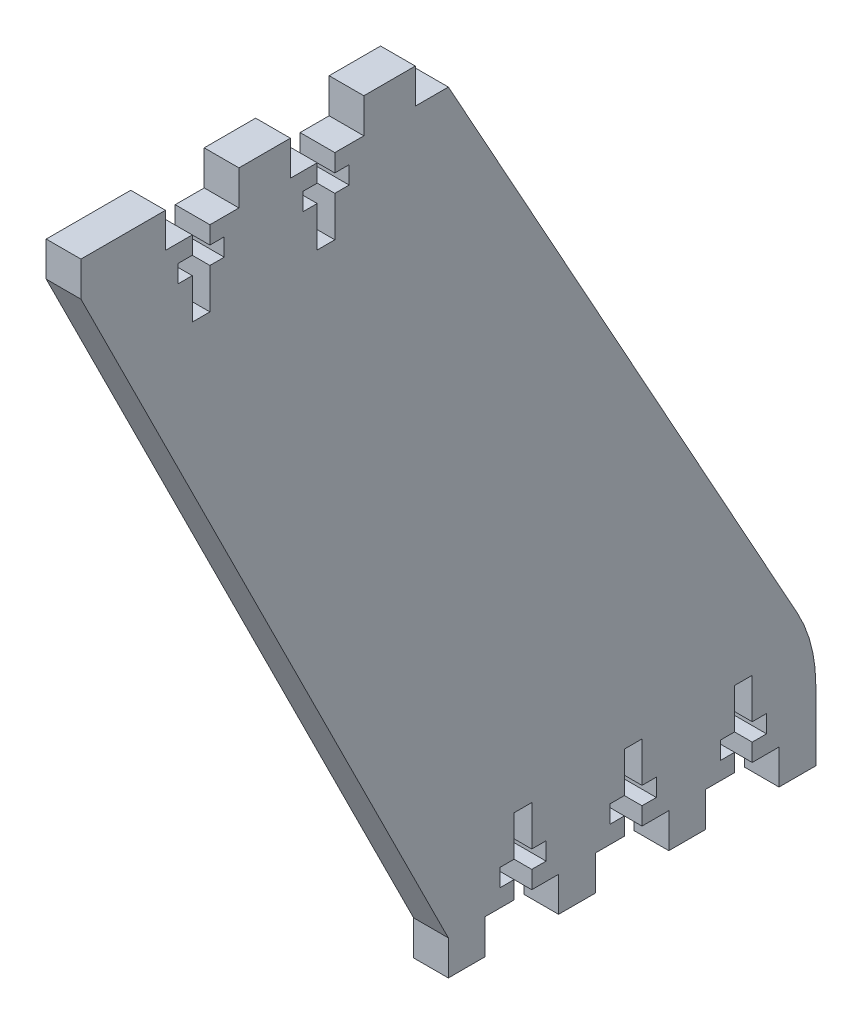
SolidWorks part; units mm, degrees
ref_plane "Front Plane" through (0, 0, 0) normal (0, 0, 1) x (1, 0, 0)
ref_plane "Top Plane" through (0, 0, 0) normal (0, 1, 0) x (1, 0, 0)
ref_plane "Right Plane" through (0, 0, 0) normal (1, 0, 0) x (0, 0, -1)
sketch "Sketch1" plane through (0, 0, 0) normal (1, 0, 0) x (0, 0, -1)
  line L0 (-74.3254, 0) -> (74.3254, 0) construction
  line L1 (-31.75, 0) -> (-95.25, 127.35)
  line L4 (-31.75, 0) -> (0, 17.1799) construction
  line L5 (-95.25, 127.35) -> (-95.25, 133.35)
  line L6 (-95.25, 133.35) -> (-80.645, 133.35)
  line L7 (-80.645, 133.35) -> (-80.645, 127.35)
  line L8 (-80.645, 127.35) -> (-67.945, 127.35)
  line L9 (-67.945, 127.35) -> (-67.945, 133.35)
  line L10 (-67.945, 133.35) -> (-59.055, 133.35)
  line L11 (-59.055, 133.35) -> (-59.055, 127.35)
  line L12 (-59.055, 127.35) -> (-46.355, 127.35)
  line L13 (-46.355, 127.35) -> (-46.355, 133.35)
  line L14 (-46.355, 133.35) -> (-37.465, 133.35)
  line L15 (-37.465, 133.35) -> (-37.465, 127.35)
  line L16 (-37.465, 127.35) -> (-31.75, 127.35)
  line L17 (-31.75, 0) -> (-31.75, -6)
  line L18 (-31.75, -6) -> (-25.4, -6)
  line L19 (-25.4, -6) -> (-25.4, 0)
  line L20 (-25.4, 0) -> (-12.7, 0)
  line L21 (-12.7, 0) -> (-12.7, -6)
  line L22 (-12.7, -6) -> (-6.35, -6)
  line L23 (-6.35, -6) -> (-6.35, 0)
  line L24 (-6.35, 0) -> (6.35, 0)
  line L25 (6.35, 0) -> (6.35, -6)
  line L26 (6.35, -6) -> (12.7, -6)
  line L27 (12.7, -6) -> (12.7, 0)
  line L28 (12.7, 0) -> (25.4, 0)
  line L29 (25.4, 0) -> (25.4, -6)
  line L30 (25.4, -6) -> (31.75, -6)
  line L31 (31.75, -6) -> (31.75, 0)
  line L32 (0, 17.1799) -> (31.75, 0) construction
  line L33 (0, 0) -> (0, 17.1799) construction
  line L34 (-63.5, 133.35) -> (-63.5, 108.2099) construction
  line L35 (31.75, 0) -> (31.75, 6.1358)
  line L36 (28.5696, 18.4423) -> (-31.75, 127.35)
  arc A0 (31.75, 6.1358) -> (28.5696, 18.4423) centre (6.35, 6.1358) ccw
  point P37 (-74.295, 127.35)
  point P38 (-52.705, 127.35)
  point P39 (-19.05, 0)
  point P40 (19.05, 0)
  point P44 (31.75, 12.7)
  line B0 (-18.8595, 13.05) -> (-18.8595, -5.9362) construction
  line B1 (-20.3835, 0) -> (-20.3835, 3.048)
  line B2 (-20.3835, 3.048) -> (-22.86, 3.048)
  line B3 (-22.86, 3.048) -> (-22.86, 6.096)
  line B4 (-22.86, 6.096) -> (-20.3835, 6.096)
  line B5 (-20.3835, 6.096) -> (-20.3835, 13.05)
  line B6 (-20.3835, 13.05) -> (-17.3355, 13.05)
  line B7 (-17.3355, 6.096) -> (-17.3355, 13.05)
  line B8 (-14.859, 6.096) -> (-17.3355, 6.096)
  line B9 (-14.859, 3.048) -> (-14.859, 6.096)
  line B10 (-17.3355, 3.048) -> (-14.859, 3.048)
  line B11 (-17.3355, 0) -> (-17.3355, 3.048)
  line B12 (0.1905, 13.05) -> (0.1905, -5.9362) construction
  line B13 (-1.3335, 0) -> (-1.3335, 3.048)
  line B14 (-1.3335, 3.048) -> (-3.81, 3.048)
  line B15 (-3.81, 3.048) -> (-3.81, 6.096)
  line B16 (-3.81, 6.096) -> (-1.3335, 6.096)
  line B17 (-1.3335, 6.096) -> (-1.3335, 13.05)
  line B18 (-1.3335, 13.05) -> (1.7145, 13.05)
  line B19 (1.7145, 6.096) -> (1.7145, 13.05)
  line B20 (4.191, 6.096) -> (1.7145, 6.096)
  line B21 (4.191, 3.048) -> (4.191, 6.096)
  line B22 (1.7145, 3.048) -> (4.191, 3.048)
  line B23 (1.7145, 0) -> (1.7145, 3.048)
  line B24 (19.2405, 13.05) -> (19.2405, -5.9362) construction
  line B25 (17.7165, 0) -> (17.7165, 3.048)
  line B26 (17.7165, 3.048) -> (15.24, 3.048)
  line B27 (15.24, 3.048) -> (15.24, 6.096)
  line B28 (15.24, 6.096) -> (17.7165, 6.096)
  line B29 (17.7165, 6.096) -> (17.7165, 13.05)
  line B30 (17.7165, 13.05) -> (20.7645, 13.05)
  line B31 (20.7645, 6.096) -> (20.7645, 13.05)
  line B32 (23.241, 6.096) -> (20.7645, 6.096)
  line B33 (23.241, 3.048) -> (23.241, 6.096)
  line B34 (20.7645, 3.048) -> (23.241, 3.048)
  line B35 (20.7645, 0) -> (20.7645, 3.048)
  line B36 (-74.4855, 114.3) -> (-74.4855, 133.2862) construction
  line B37 (-72.9615, 127.35) -> (-72.9615, 124.302)
  line B38 (-72.9615, 124.302) -> (-70.485, 124.302)
  line B39 (-70.485, 124.302) -> (-70.485, 121.254)
  line B40 (-70.485, 121.254) -> (-72.9615, 121.254)
  line B41 (-72.9615, 121.254) -> (-72.9615, 114.3)
  line B42 (-72.9615, 114.3) -> (-76.0095, 114.3)
  line B43 (-76.0095, 121.254) -> (-76.0095, 114.3)
  line B44 (-78.486, 121.254) -> (-76.0095, 121.254)
  line B45 (-78.486, 124.302) -> (-78.486, 121.254)
  line B46 (-76.0095, 124.302) -> (-78.486, 124.302)
  line B47 (-76.0095, 127.35) -> (-76.0095, 124.302)
  line B48 (-52.8955, 114.3) -> (-52.8955, 133.2862) construction
  line B49 (-51.3715, 127.35) -> (-51.3715, 124.302)
  line B50 (-51.3715, 124.302) -> (-48.895, 124.302)
  line B51 (-48.895, 124.302) -> (-48.895, 121.254)
  line B52 (-48.895, 121.254) -> (-51.3715, 121.254)
  line B53 (-51.3715, 121.254) -> (-51.3715, 114.3)
  line B54 (-51.3715, 114.3) -> (-54.4195, 114.3)
  line B55 (-54.4195, 121.254) -> (-54.4195, 114.3)
  line B56 (-56.896, 121.254) -> (-54.4195, 121.254)
  line B57 (-56.896, 124.302) -> (-56.896, 121.254)
  line B58 (-54.4195, 124.302) -> (-56.896, 124.302)
  line B59 (-54.4195, 127.35) -> (-54.4195, 124.302)
  dimension "D12" = 25.4
  dimension "D2" = 63.5
  dimension "D3" = 63.5
  dimension "D4" = 6
  dimension "D5" = 6
  dimension "D6" = 133.35
  dimension "D7" = 12.7
  dimension "D8" = 63.5
  dimension "D9" = 12.7
  dimension "D10" = 6.35
  dimension "D11" = 12.7
  dimension "D13" = 8.89
  dimension "D14" = 5.715
sketch_block_instance "Block-6-32x0_625 T-Nut block-1"
sketch_block "Block-6-32x0_625 T-Nut block" parameters "D1"=3.048, "D2"=13.05, "D3"=8.001, "D4"=3.048, "D5"=3.048
sketch_block_instance "Block-6-32x0_625 T-Nut block-2"
sketch_block_instance "Block-6-32x0_625 T-Nut block-3"
sketch_block_instance "Block-6-32x0_625 T-Nut block-5"
sketch_block_instance "Block-6-32x0_625 T-Nut block-6"
extrude "Boss-Extrude1" add sketch "Sketch1" along normal blind 6 contours L28 L29 L30 L31 L35 A0 L36 L16 L15 L14 L13 L12 L11 L10 L9 L8 L7 L6 L5 L1 L17 L18 L19 L20 region at (0, 63.5922, 30.2578)
